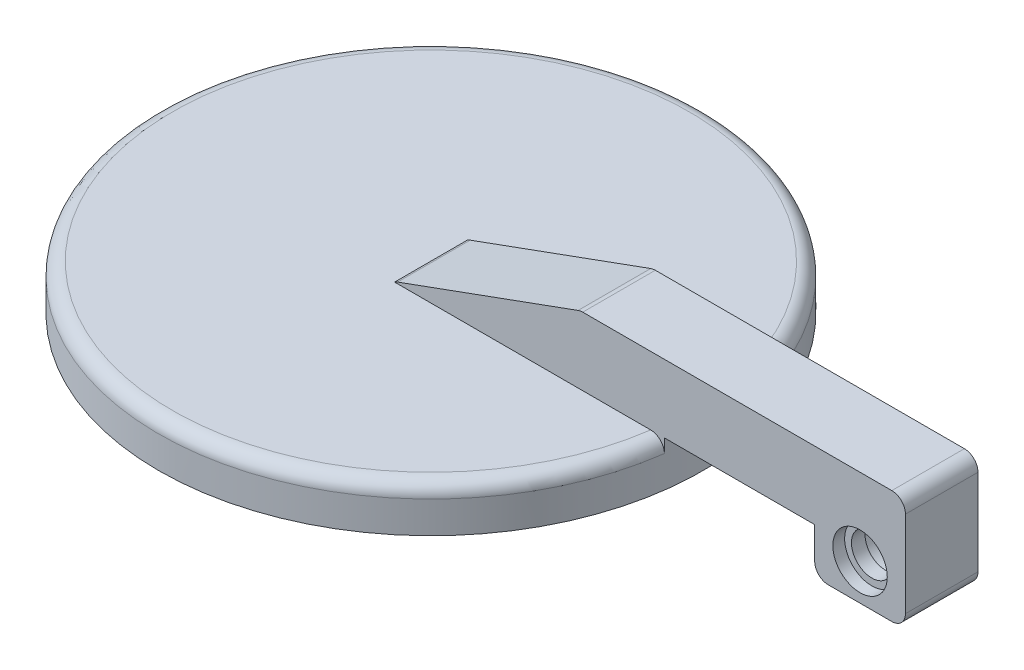
SolidWorks part; units mm, degrees
ref_plane "Front Plane" through (0, 0, 0) normal (0, 0, 1) x (1, 0, 0)
ref_plane "Top Plane" through (0, 0, 0) normal (0, 1, 0) x (1, 0, 0)
ref_plane "Right Plane" through (0, 0, 0) normal (1, 0, 0) x (0, 0, -1)
sketch "Sketch2" plane through (0, 0, 0) normal (0, 0, 1) x (1, 0, 0)
  line L7 (0, 0) -> (30, 0)
  line L8 (0, 0) -> (0, 5)
  line L9 (0, 5) -> (30, 5)
  line L10 (30, 0) -> (30, 5)
  dimension "D1" = 5
  dimension "D2" = 30
revolve "Revolve1" add sketch "Sketch2" angle 360 about L8
sketch "Sketch3" plane through (0, 5, 0) normal (0, 1, 0) x (1, 0, 0)
  line L0 (0, -10) -> (0, 10) construction
  line L1 (0, 10) -> (35, 10)
  line L2 (35, 10) -> (35, 6)
  line L3 (35, 6) -> (0, 6)
  line L4 (0, 10) -> (0, 6)
  line L5 (0, -10) -> (35, -10)
  line L6 (35, -10) -> (35, -6)
  line L7 (35, -6) -> (0, -6)
  line L8 (0, -6) -> (0, -10)
  line L9 (0, 4) -> (0, -4)
  line L10 (0, 4) -> (56.3, 4)
  line L11 (0, -4) -> (56.3, -4)
  line L12 (56.3, -4) -> (56.3, 4)
  point P4 (0, 0)
  point P13 (0, 0)
  circle M1 centre (0, 0) radius 30
  dimension "D1" = 20
  dimension "D2" = 35
  dimension "D3" = 4
  dimension "0.7" = 8
  dimension "D5" = 56.3
extrude "Boss-Extrude1" add sketch "Sketch3" along normal blind 7.5 contours L9 L11 L10 M1 | L11 L12 L10 M1 region at (14.9555, 5, 0) region at (43.1053, 5, 0)
sketch "Sketch4" plane through (0, 0, 0) normal (0, 0, 1) x (1, 0, 0)
  line L5 (35, 8.75) -> (37.8, 8.75) construction
  line L7 (56.3, 8.75) -> (37.8, 8.75) construction
  line L8 (56.3, 12.5) -> (56.3, 5) construction
  line L10 (-0.1339, 5) -> (20.4721, 12.5)
  line L11 (29.7321, 5) -> (-30, 5) construction
  line L12 (0, 12.5) -> (56.3, 12.5) construction
  line L13 (0, 5) -> (29.7321, 5) construction
  line L14 (20.4721, 12.5) -> (0, 12.5)
  line L15 (0, 12.5) -> (-0.1339, 5)
  circle A0 centre (37.8, 8.75) radius 2
  dimension "D3" = 4
  dimension "D1" = 20
  dimension "D2" = 18.5
extrude "Cut-Extrude1" cut sketch "Sketch4" against normal mid plane 30 contours L14 L15 L10
sketch "Sketch6" plane through (0, 5, 0) normal (0, -1, 0) x (1, 0, 0)
  line L6 (56.3, 4) -> (46.3, 4)
  line L7 (56.3, 4) -> (56.3, -4) construction
  line L8 (29.7321, 4) -> (56.3, 4) construction
  line L9 (46.3, 4) -> (46.3, -4)
  line L10 (29.7321, -4) -> (56.3, -4) construction
  line L11 (46.3, -4) -> (56.3, -4)
  line L12 (56.3, -4) -> (56.3, 4)
  dimension "D1" = 10
extrude "Boss-Extrude2" add sketch "Sketch6" along normal blind 5
sketch "Sketch7" plane through (0, 0, 4) normal (0, 0, 1) x (1, 0, 0)
  line L0 (51.3, 4) -> (51.3, 0) construction
  line L2 (56.3, 0) -> (46.3, 0) construction
  circle A0 centre (51.3, 4) radius 3
  dimension "D2" = 6
  dimension "D1" = 4
extrude "Cut-Extrude2" cut sketch "Sketch7" against normal blind 10
fillet "Fillet2" radius 1.5 6 edges at (46.3, 0, 0) (56.3, 0, 0) (56.3, 12.5, 0) (20.4721, 12.5, 0) (0, 5.0487, 0) (-30, 5, 0)
sketch "Sketch9" plane through (0, 0, -4) normal (0, 0, -1) x (-1, 0, 0)
  circle A0 centre (-51.3, 4) radius 3
  circle A1 centre (-51.3, 4) radius 4
  dimension "D1" = 6
  dimension "D2" = 8
sketch "Sketch10" plane through (0, 0, 4) normal (0, 0, 1) x (1, 0, 0)
  circle A0 centre (51.3, 4) radius 3
  circle A1 centre (51.3, 4) radius 2.25
  dimension "D1" = 6
  dimension "D2" = 4.5
extrude "Boss-Extrude4" add sketch "Sketch10" along normal blind 1.5 from offset 2.8 offset against normal yes
sketch "Sketch11" plane through (0, 0, 1.2) normal (0, 0, -1) x (-1, 0, 0)
  circle A0 centre (-51.3, 4) radius 2.6
  circle A1 centre (-51.3, 4) radius 3
  dimension "D1" = 5.2
extrude "Boss-Extrude5" add sketch "Sketch11" along normal blind 5.2
sketch "Sketch12" plane through (0, 0, 0) normal (0, -1, 0) x (1, 0, 0)
  line L0 (0, 30) -> (0, 25.5) construction
  circle A0 centre (0, 0) radius 30 construction
  circle A1 centre (0, 27.75) radius 1.1
  circle A2 centre (19.6222, 19.6222) radius 1.1
  circle A3 centre (27.75, 0) radius 1.1
  circle A4 centre (19.6222, -19.6222) radius 1.1
  circle A5 centre (0, -27.75) radius 1.1
  circle A6 centre (-19.6222, -19.6222) radius 1.1
  circle A7 centre (-27.75, 0) radius 1.1
  circle A8 centre (-19.6222, 19.6222) radius 1.1
  point P24 (0, 0)
  dimension "D2" = 2.2
  dimension "D1" = 4.5
  dimension "D3" = 8
extrude "Cut-Extrude3" cut sketch "Sketch12" against normal blind 0.5
